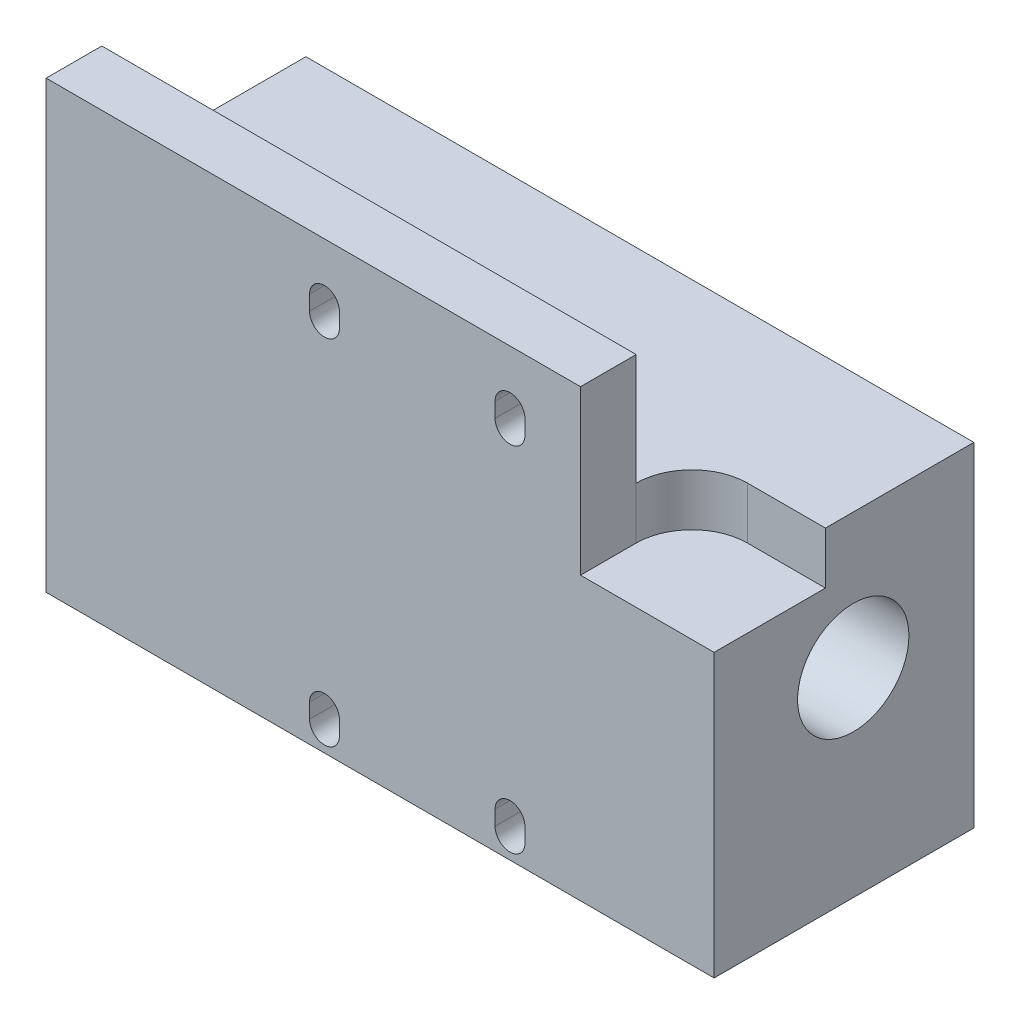
SolidWorks part; units mm, degrees
material "Delrin 2700 NC010, Low Viscosity Acetal Copolymer (SS)"
ref_plane "Front Plane" through (0, 0, 0) normal (0, 0, 1) x (1, 0, 0)
ref_plane "Top Plane" through (0, 0, 0) normal (0, 1, 0) x (1, 0, 0)
ref_plane "Right Plane" through (0, 0, 0) normal (1, 0, 0) x (0, 0, -1)
sketch "Sketch1" plane through (0, 0, 0) normal (1, 0, 0) x (0, 0, -1)
  line L1 (-22.225, 38.1) -> (22.225, 38.1)
  line L2 (-22.225, 38.1) -> (-22.225, -38.1)
  line L3 (-22.225, -38.1) -> (22.225, -38.1)
  line L4 (22.225, 38.1) -> (22.225, -38.1)
  line L5 (-22.225, 38.1) -> (22.225, -38.1) construction
  line L6 (-22.225, -38.1) -> (22.225, 38.1) construction
  point P0 (0, 0)
  dimension "D1" = 44.45
  dimension "D2" = 76.2
extrude "Boss-Extrude1" add sketch "Sketch1" along normal blind 114.3
sketch "Sketch2" plane through (114.3, 0, 0) normal (1, 0, 0) x (0, 0, -1)
  line L0 (-22.225, 38.1) -> (-22.225, -38.1) construction
  line L1 (22.225, 38.1) -> (-22.225, 38.1) construction
  circle A0 centre (1.588, -4.0132) radius 9.525
  dimension "D1" = 19.05
  dimension "D3" = 42.1132
  dimension "D2" = 23.813
extrude "Cut-Extrude1" cut sketch "Sketch2" against normal up to next
sketch "Sketch3" plane through (0, 0, 22.225) normal (0, 0, 1) x (1, 0, 0)
  line L1 (114.3, 38.1) -> (91.44, 38.1)
  line L2 (114.3, 38.1) -> (114.3, 10.16)
  line L3 (114.3, 10.16) -> (91.44, 10.16)
  line L4 (91.44, 38.1) -> (91.44, 10.16)
  dimension "D1" = 22.86
  dimension "D2" = 27.94
extrude "Cut-Extrude2" cut sketch "Sketch3" against normal blind 19.05
sketch "Sketch4" plane through (0, 0, 0) normal (1, 0, 0) x (0, 0, -1)
  line L1 (22.225, 38.1) -> (-12.7, 38.1)
  line L2 (22.225, 38.1) -> (22.225, 19.05)
  line L3 (22.225, 19.05) -> (-12.7, 19.05)
  line L4 (-12.7, 38.1) -> (-12.7, 19.05)
  dimension "D1" = 34.925
  dimension "D2" = 19.05
extrude "Cut-Extrude3" cut sketch "Sketch4" along normal up to next
fillet "Fillet1" radius 9.525 1 edges at (91.44, 14.605, 3.175)
hole_wizard "#10 Clearance Hole1" positions "Sketch7" profile "Sketch8" hole size "#10" standard "ANSI Inch" end condition up to next
sketch "Sketch7" plane through (0, 0, -22.225) normal (0, 0, -1) x (-1, 0, 0)
  line L1 (-47.625, 28.6385) -> (-79.375, 28.6385) construction
  line L2 (-47.625, 28.6385) -> (-47.625, -31.8135) construction
  line L3 (-47.625, -31.8135) -> (-79.375, -31.8135) construction
  line L4 (-79.375, 28.6385) -> (-79.375, -31.8135) construction
  line L5 (-79.375, 28.6385) -> (-47.625, -31.8135) construction
  line L7 (-63.5, -1.5875) -> (0, -1.5875) construction
  line L8 (-114.3, -38.1) -> (0, -38.1) construction
  line L9 (0, -38.1) -> (0, 19.05) construction
  point P1 (-47.625, 28.6385)
  point P2 (-79.375, -31.8135)
  point P201 (-47.625, -31.8135)
  point P202 (-79.375, 28.6385)
  dimension "D1" = 31.75
  dimension "D2" = 60.452
  dimension "D3" = 63.5
  dimension "D4" = 36.5125
sketch "Sketch8" plane through (47.625, 28.6385, -22.225) normal (1, 0, 0) x (0, 1, 0)
  line L0 (0, 0) -> (0, 44.45)
  line L1 (0, 44.45) -> (2.5527, 44.45)
  line L2 (2.5527, 44.45) -> (2.5527, 0)
  line L5 (2.5527, 0) -> (0, 0)
  line L11 (0, -6.35) -> (0, 107.95) construction
  dimension "Thru Hole Dia." = 5.1054
  dimension "Thru Hole Depth" = 44.45
sketch "Sketch9" plane through (0, 0, 22.225) normal (0, 0, 1) x (1, 0, 0)
  line L0 (47.625, 28.6385) -> (47.625, 26.0985) construction
  line L1 (50.1777, 28.6385) -> (50.1777, 26.0985)
  line L2 (45.0723, 28.6385) -> (45.0723, 26.0985)
  line L3 (79.375, 28.6385) -> (79.375, 26.0985) construction
  line L4 (81.9277, 28.6385) -> (81.9277, 26.0985)
  line L5 (76.8223, 28.6385) -> (76.8223, 26.0985)
  line L6 (79.375, -31.8135) -> (79.375, -34.3535) construction
  line L7 (81.9277, -31.8135) -> (81.9277, -34.3535)
  line L8 (76.8223, -31.8135) -> (76.8223, -34.3535)
  line L9 (47.625, -31.8135) -> (47.625, -34.3535) construction
  line L11 (50.1777, -31.8135) -> (50.1777, -34.3535)
  line L12 (45.0723, -31.8135) -> (45.0723, -34.3535)
  arc A0 (50.1777, 28.6385) -> (45.0723, 28.6385) centre (47.625, 28.6385) ccw
  arc A1 (45.0723, 26.0985) -> (50.1777, 26.0985) centre (47.625, 26.0985) ccw
  arc A2 (81.9277, 28.6385) -> (76.8223, 28.6385) centre (79.375, 28.6385) ccw
  arc A3 (76.8223, 26.0985) -> (81.9277, 26.0985) centre (79.375, 26.0985) ccw
  arc A4 (81.9277, -31.8135) -> (76.8223, -31.8135) centre (79.375, -31.8135) ccw
  arc A5 (76.8223, -34.3535) -> (81.9277, -34.3535) centre (79.375, -34.3535) ccw
  arc A6 (50.1777, -31.8135) -> (45.0723, -31.8135) centre (47.625, -31.8135) ccw
  arc A7 (45.0723, -34.3535) -> (50.1777, -34.3535) centre (47.625, -34.3535) ccw
  circle A8 centre (47.625, 28.6385) radius 2.5527 construction
  circle A9 centre (79.375, 28.6385) radius 2.5527 construction
  circle A10 centre (79.375, -31.8135) radius 2.5527 construction
  circle A11 centre (47.625, -31.8135) radius 2.5527 construction
  point P2 (47.625, 27.3685)
  point P8 (79.375, 27.3685)
  point P15 (79.375, -33.0835)
  point P22 (47.625, -33.0835)
  dimension "D1" = 2.54
extrude "Cut-Extrude4" cut sketch "Sketch9" against normal up to next
